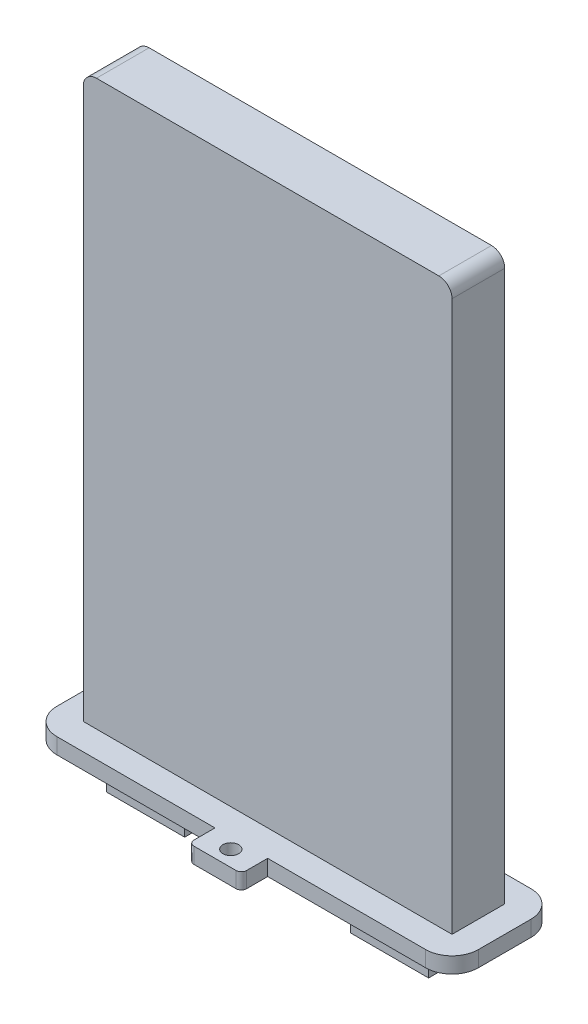
SolidWorks part; units mm, degrees
ref_plane "Front Plane" through (0, 0, 0) normal (0, 0, 1) x (1, 0, 0)
ref_plane "Top Plane" through (0, 0, 0) normal (0, 1, 0) x (1, 0, 0)
ref_plane "Right Plane" through (0, 0, 0) normal (1, 0, 0) x (0, 0, -1)
sketch "Sketch1" plane through (0, 0, 0) normal (0, 0, 1) x (1, 0, 0)
  line L1 (-35, 55) -> (35, 55)
  line L2 (-35, 55) -> (-35, -55)
  line L3 (-35, -55) -> (35, -55)
  line L4 (35, 55) -> (35, -55)
  line L5 (-35, 55) -> (35, -55) construction
  line L6 (-35, -55) -> (35, 55) construction
  point P0 (0, 0)
  dimension "D1" = 70
  dimension "D2" = 110
extrude "Boss-Extrude1" add sketch "Sketch1" along normal blind 10
fillet "Fillet1" radius 2.5 2 edges at (35, 55, 5) (-35, 55, 5)
sketch "Sketch3" plane through (0, 0, 0) normal (0, 0, -1) x (-1, 0, 0)
  line L0 (0, -55) -> (0, -45) construction
  line L1 (35, -55) -> (-35, -55) construction
  line L2 (-32.5, 55) -> (32.5, 55) construction
  line L9 (-20.75, -58.6) -> (-15.75, -58.6)
  line L10 (-30.55, -58.6) -> (-25.55, -58.6)
  line L11 (-30.55, -58.6) -> (-30.55, -61.4)
  line L12 (-30.55, -61.4) -> (-15.75, -61.4)
  line L13 (-15.75, -58.6) -> (-15.75, -61.4)
  line L14 (-30.55, -58.6) -> (-15.75, -61.4) construction
  line L15 (-30.55, -61.4) -> (-15.75, -58.6) construction
  line L16 (-25.55, -55) -> (-20.75, -55)
  line L17 (-25.55, -55) -> (-25.55, -58.6)
  line L19 (-20.75, -55) -> (-20.75, -58.6)
  line L20 (-25.55, -55) -> (-20.75, -58.6) construction
  line L21 (-25.55, -58.6) -> (-20.75, -55) construction
  line L22 (30.55, -58.6) -> (30.55, -61.4)
  line L23 (30.55, -61.4) -> (15.75, -61.4)
  line L24 (15.75, -58.6) -> (15.75, -61.4)
  line L25 (20.75, -58.6) -> (15.75, -58.6)
  line L26 (20.75, -55) -> (20.75, -58.6)
  line L27 (25.55, -55) -> (20.75, -55)
  line L28 (25.55, -55) -> (25.55, -58.6)
  line L29 (30.55, -58.6) -> (25.55, -58.6)
  point P5 (0, -50)
  point P12 (-23.15, -60)
  point P17 (-23.15, -56.8)
  dimension "D1" = 110
  dimension "D3" = 2.8
  dimension "D4" = 14.8
  dimension "D5" = 4.8
  dimension "D6" = 3.6
extrude "Boss-Extrude3" add sketch "Sketch3" against normal blind 10
sketch "Sketch5" plane through (0, -55, 0) normal (0, -1, 0) x (1, 0, 0)
  line L0 (0, 10) -> (0, 0) construction
  line L1 (-20.75, 10) -> (20.75, 10) construction
  line L2 (5, -5) -> (35, -5)
  line L3 (-35, 10) -> (35, 10)
  line L4 (-35, 10) -> (-35, 0)
  line L5 (-35, 0) -> (35, 0)
  line L6 (35, 10) -> (35, 0)
  line L7 (-35, 10) -> (35, 0) construction
  line L8 (-35, 0) -> (35, 10) construction
  line L9 (-35, 15) -> (-5, 15)
  line L10 (-40, 10) -> (-40, 0)
  line L11 (-35, -5) -> (-5, -5)
  line L12 (40, 10) -> (40, 0)
  line L13 (-40, 15) -> (40, -5) construction
  line L14 (-40, -5) -> (40, 15) construction
  line L16 (-5, -5) -> (-5, -9)
  line L17 (-4, -10) -> (4, -10)
  line L18 (5, -5) -> (5, -9)
  line L20 (-40, 5) -> (40, 5) construction
  line L21 (-5, 15) -> (-5, 19)
  line L22 (5, 15) -> (5, 19)
  line L23 (-4, 20) -> (4, 20)
  line L24 (5, 15) -> (35, 15)
  arc A0 (35, 15) -> (40, 10) centre (35, 10) cw
  arc A1 (35, -5) -> (40, 0) centre (35, 0) ccw
  arc A2 (-40, 0) -> (-35, -5) centre (-35, 0) ccw
  arc A3 (-35, 15) -> (-40, 10) centre (-35, 10) ccw
  circle A4 centre (0, -7) radius 1.5
  arc A5 (-5, -9) -> (-4, -10) centre (-4, -9) ccw
  arc A6 (4, -10) -> (5, -9) centre (4, -9) ccw
  circle A7 centre (0, 17) radius 1.5
  arc A8 (-5, 19) -> (-4, 20) centre (-4, 19) cw
  arc A9 (4, 20) -> (5, 19) centre (4, 19) cw
  point P5 (0, 5)
  point P11 (0, 5)
  point P37 (-5, -10)
  dimension "D3" = 5
  dimension "D6" = 3
  dimension "D7" = 1
  dimension "D1" = 20
  dimension "D2" = 80
  dimension "D4" = 5
  dimension "D5" = 10
  dimension "D8" = 3
extrude "Boss-Extrude5" add sketch "Sketch5" against normal blind 3
